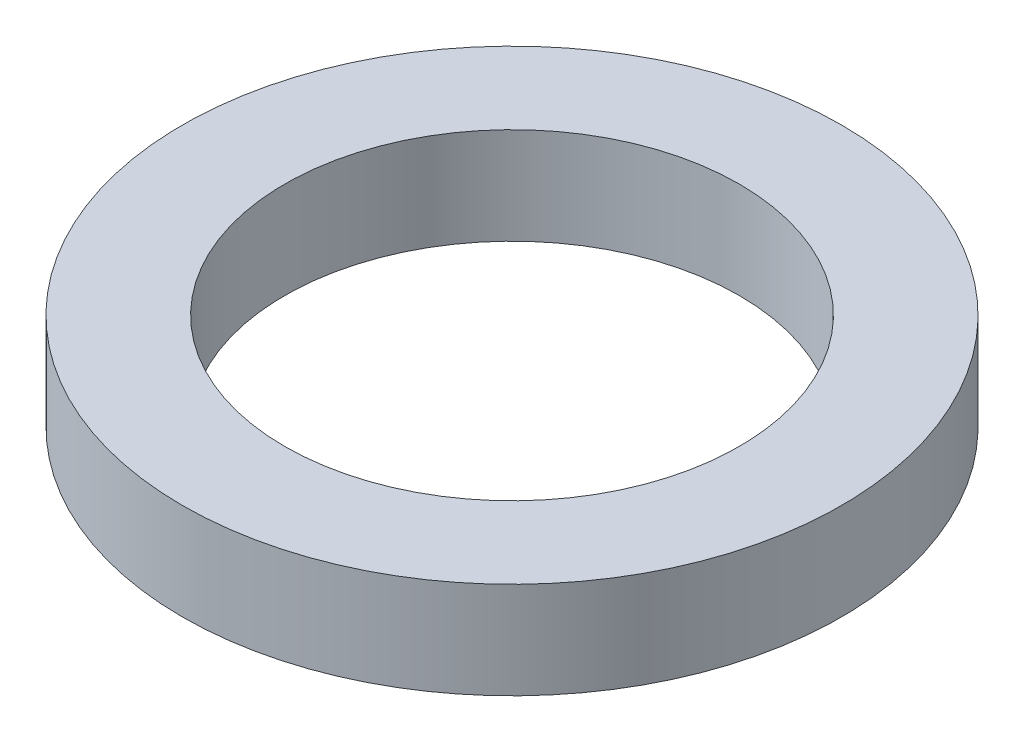
SolidWorks part; units mm, degrees
ref_plane "Przednia" through (0, 0, 0) normal (0, 0, 1) x (1, 0, 0)
ref_plane "Górna" through (0, 0, 0) normal (0, 1, 0) x (1, 0, 0)
ref_plane "Prawa" through (0, 0, 0) normal (1, 0, 0) x (0, 0, -1)
sketch "Szkic1" plane through (0, 0, 0) normal (0, 1, 0) x (1, 0, 0)
  circle A0 centre (0, 0) radius 4
  circle A1 centre (0, 0) radius 5.8
  dimension "D1" = 1.8
  dimension "D2" = 8
extrude "Dodanie-wyciągnięcie1" add sketch "Szkic1" along normal blind 1.7
